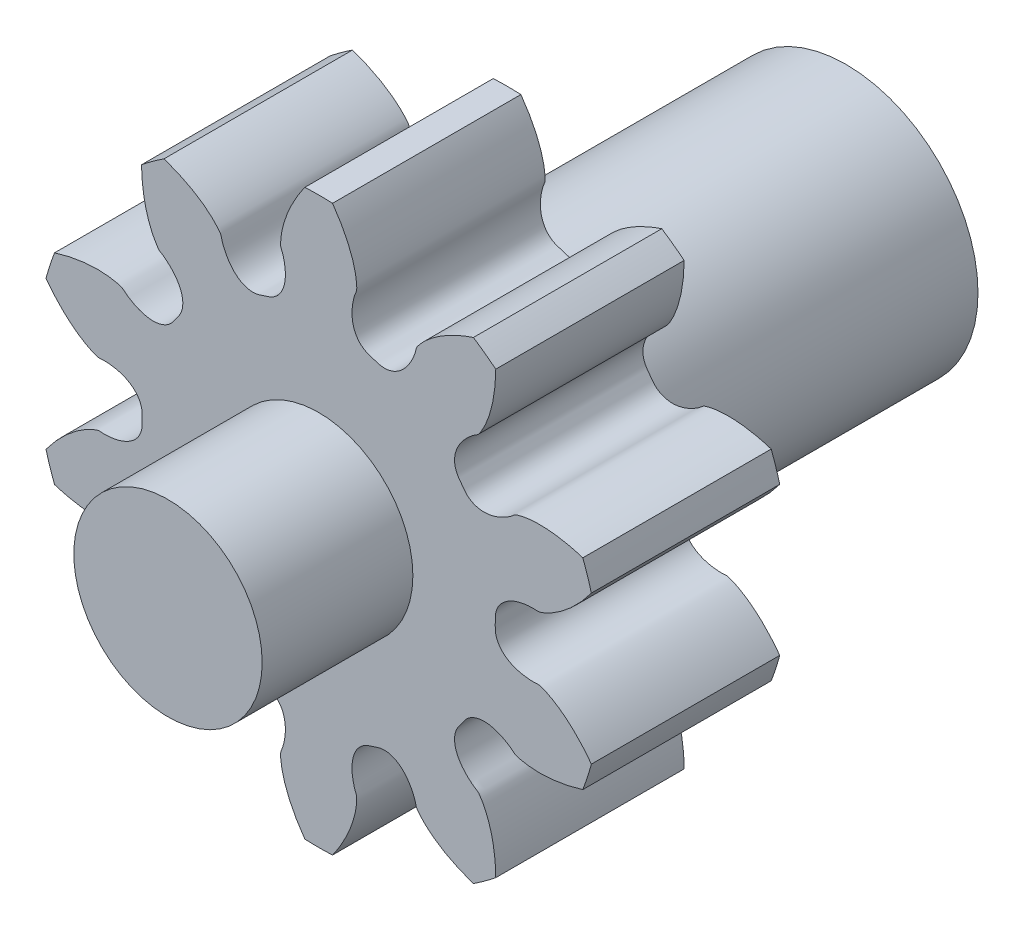
SolidWorks part; units mm, degrees
ref_plane "Front Plane" through (0, 0, 0) normal (0, 0, 1) x (1, 0, 0)
ref_plane "Top Plane" through (0, 0, 0) normal (0, 1, 0) x (1, 0, 0)
ref_plane "Right Plane" through (0, 0, 0) normal (1, 0, 0) x (0, 0, -1)
ref_axis "Axis1" through (0, 0, 55) along (0, 0, -1)
sketch "SketchRevolveSpurPinion" plane through (0, 0, 0) normal (1, 0, 0) x (0, 0, -1)
  line L0 (0, 0) -> (1, 0) construction
  line L1 (-5, 0) -> (-5, 15)
  line L2 (-5, 15) -> (5, 15)
  line L3 (5, 15) -> (5, 0)
  line L4 (5, 0) -> (-5, 0)
  dimension "Side1" = 5
  dimension "OutsideRadius" = 15
  dimension "Side2" = 5
revolve "SpurPinion" add sketch "SketchRevolveSpurPinion" angle 360 about L0
sketch "SketchToothSpurPinion" plane through (0, 0, 0) normal (0, 0, 1) x (1, 0, 0)
  arc A0 (14.5696, 4.0612) -> (14.5696, -4.0612) centre (0, 0) cw
  spline S0 degree 3 poles (14.5696, -4.0612) (14.4279, -3.8616) (14.2097, -3.578) (13.9044, -3.2288) (13.685, -2.9973) (13.4702, -2.7885) (13.2616, -2.6014) (13.0604, -2.4352) (12.8681, -2.289) (12.6858, -2.1617) (12.5149, -2.0524) (12.3563, -1.9598) (12.2112, -1.8827) (12.0805, -1.8201) (11.9652, -1.7699) (11.8428, -1.7244) (11.6492, -1.6493) (11.4346, -1.6969) (11.2391, -1.6839) (11.1188, -1.6757) (11.0016, -1.6626) (10.8872, -1.6459) (10.7757, -1.6253) (10.6672, -1.6008) (10.5615, -1.5723) (10.4588, -1.5399) (10.3591, -1.5035) (10.2623, -1.4628) (10.1684, -1.4177) (10.0776, -1.368) (9.9899, -1.3135) (9.9055, -1.2537) (9.8246, -1.1883) (9.7476, -1.1169) (9.675, -1.0391) (9.6075, -0.9545) (9.5461, -0.8628) (9.4917, -0.7639) (9.4458, -0.658) (9.4098, -0.5457) (9.3848, -0.4282) (9.3744, -0.3207) (9.3704, -0.1777) (9.3783, 0) (9.3704, 0.1777) (9.3744, 0.3207) (9.3848, 0.4282) (9.4098, 0.5457) (9.4458, 0.658) (9.4917, 0.7639) (9.5461, 0.8628) (9.6075, 0.9545) (9.675, 1.0391) (9.7476, 1.1169) (9.8246, 1.1883) (9.9055, 1.2537) (9.9899, 1.3135) (10.0776, 1.368) (10.1684, 1.4177) (10.2623, 1.4628) (10.3591, 1.5035) (10.4588, 1.5399) (10.5615, 1.5723) (10.6672, 1.6008) (10.7757, 1.6253) (10.8872, 1.6459) (11.0016, 1.6626) (11.1188, 1.6757) (11.2391, 1.6839) (11.4346, 1.6969) (11.6492, 1.6493) (11.8428, 1.7244) (11.9652, 1.7699) (12.0805, 1.8201) (12.2112, 1.8827) (12.3563, 1.9598) (12.5149, 2.0524) (12.6858, 2.1617) (12.8681, 2.289) (13.0604, 2.4352) (13.2616, 2.6014) (13.4702, 2.7885) (13.685, 2.9973) (13.9044, 3.2288) (14.2097, 3.578) (14.4279, 3.8616) (14.5696, 4.0612) knots 0 0 0 0 0.05171 0.075524 0.097977 0.119069 0.138801 0.157172 0.174182 0.189831 0.204119 0.217047 0.228613 0.238819 0.247664 0.255149 0.266491 0.290789 0.299455 0.307937 0.316241 0.324377 0.332355 0.340185 0.347882 0.355458 0.36293 0.370317 0.377638 0.384917 0.392177 0.399447 0.406755 0.414132 0.42161 0.429216 0.436977 0.444911 0.453028 0.461323 0.469778 0.478358 0.484106 0.5 0.515894 0.521642 0.530222 0.538677 0.546972 0.555089 0.563023 0.570784 0.57839 0.585868 0.593245 0.600553 0.607823 0.615083 0.622362 0.629683 0.63707 0.644542 0.652118 0.659815 0.667645 0.675623 0.683759 0.692063 0.700545 0.709211 0.733509 0.744851 0.752336 0.761181 0.771387 0.782953 0.795881 0.810169 0.825818 0.842828 0.861199 0.880931 0.902023 0.924476 0.94829 1 1 1 1
extrude "ToothExtrudeCutSpurPinion" cut sketch "SketchToothSpurPinion" against normal blind 5 and the other way blind 5
pattern_circular "PatternSpurPinion" count 10 over 360 about axis through (0, 0, 55) along (0, 0, -1) of "ToothExtrudeCutSpurPinion"
sketch "BoreRevolveSketch" plane through (0, 0, 0) normal (1, 0, 0) x (0, 0, -1)
  line L0 (0, 0) -> (1, 0) construction
sketch "AuxiliarySketchSpurPinion" plane through (0, 0, 0) normal (0, 0, 1) x (1, 0, 0)
  circle A0 centre (0, 0) radius 12.5 construction
  circle A1 centre (0, 0) radius 11.7462 construction
  circle A2 centre (0, 0) radius 12.2336 construction
  circle A3 centre (0, 0) radius 15 construction
  circle A4 centre (0, 0) radius 9.375 construction
  dimension "PitchDiameter" = 25
  dimension "BaseDiameter" = 23.4923
  dimension "FormDiameter" = 24.4671
  dimension "MajorDiameter" = 30
  dimension "MinorDiameter" = 18.75
sketch "Sketch3" plane through (0, 0, 5) normal (0, 0, 1) x (1, 0, 0)
  circle A0 centre (0, 0) radius 5
extrude "Boss-Extrude1" add sketch "Sketch3" along normal blind 8
sketch "Sketch4" plane through (0, 0, -5) normal (0, 0, -1) x (-1, 0, 0)
  circle A2 centre (0, 0) radius 7
extrude "Boss-Extrude2" add sketch "Sketch4" along normal blind 18
sketch "Sketch6" plane through (0, 0, -23) normal (0, 0, -1) x (-1, 0, 0)
  line L2 (-2.6458, -3) -> (2.6458, -3)
  arc A4 (2.6458, -3) -> (-2.6458, -3) centre (0, 0) ccw
extrude "Cut-Extrude2" cut sketch "Sketch6" against normal blind 15 contours A4 L2
